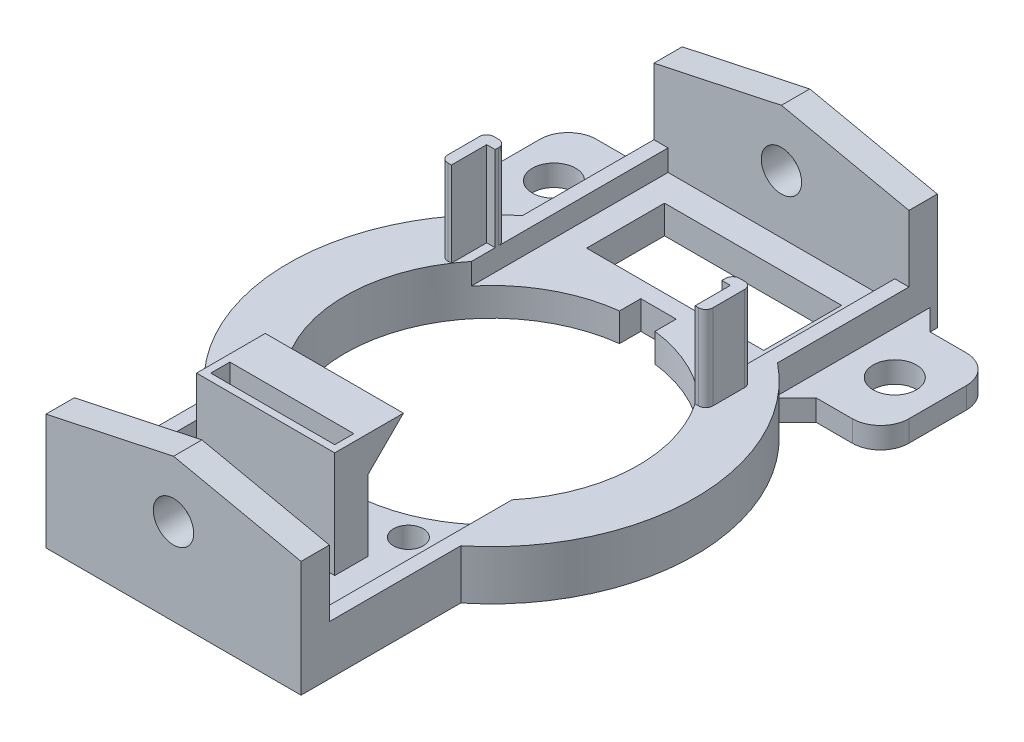
SolidWorks part; units mm, degrees
ref_plane "Front Plane" through (0, 0, 0) normal (0, 0, 1) x (1, 0, 0)
ref_plane "Top Plane" through (0, 0, 0) normal (0, 1, 0) x (1, 0, 0)
ref_plane "Right Plane" through (0, 0, 0) normal (1, 0, 0) x (0, 0, -1)
sketch "Sketch1" plane through (0, 0, 0) normal (0, 0, 1) x (1, 0, 0)
  line L3 (-18, 114.7896) -> (0, 114.7896)
  line L4 (0, 114.7896) -> (18, 114.7896)
  line L7 (0, 118.6383) -> (-38.0273, 110.5073) construction
  line L9 (38.0273, 110.5073) -> (0, 118.6383) construction
  line L11 (18, 114.7896) -> (18, 121.7896)
  line L12 (18, 121.7896) -> (16, 121.7896)
  line L13 (16, 121.7896) -> (16, 118.7896)
  line L14 (16, 118.7896) -> (-16, 118.7896)
  line L15 (-16, 118.7896) -> (-16, 121.7896)
  line L16 (-16, 121.7896) -> (-18, 121.7896)
  line L17 (-18, 121.7896) -> (-18, 114.7896)
  point P15 (0, 118.7896)
  dimension "D1" = 32
  dimension "D2" = 2
  dimension "D3" = 3
  dimension "D4" = 4
extrude "Boss-Extrude1" add sketch "Sketch1" along normal up to surface (89.8 mm away)
sketch "Sketch2" plane through (0, 114.7896, 0) normal (0, -1, 0) x (1, 0, 0)
  line L0 (18, 89.8) -> (18, 0) construction
  line L5 (-14, 54.9) -> (14, 54.9)
  line L6 (-14, 54.9) -> (-14, 34.9)
  line L7 (-14, 34.9) -> (14, 34.9)
  line L8 (14, 54.9) -> (14, 34.9)
  point P4 (0, 34.9)
  point P8 (18, 44.9)
  point P9 (14, 44.9)
  dimension "D1" = 4
  dimension "D2" = 20
extrude "Cut-Extrude1" [suppressed] cut sketch "Sketch2" against normal up to next
sketch "Sketch3" plane through (-18, 0, 0) normal (-1, 0, 0) x (0, 0, 1)
  line L0 (89.8, 121.7896) -> (0, 121.7896) construction
  line L1 (40.65, 118.7896) -> (49.15, 118.7896)
  line L2 (40.65, 118.7896) -> (40.65, 121.7896)
  line L3 (40.65, 121.7896) -> (49.15, 121.7896)
  line L4 (49.15, 118.7896) -> (49.15, 121.7896)
  line L5 (89.8, 118.7896) -> (0, 118.7896) construction
  point P9 (44.9, 121.7896)
  point P10 (44.9, 121.7896)
  dimension "D1" = 8.5
extrude "Cut-Extrude2" [suppressed] cut sketch "Sketch3" against normal through all
sketch "Sketch4" plane through (0, 118.7896, 0) normal (0, 1, 0) x (1, 0, 0)
  circle A0 centre (7.75, -23.25) radius 2.1 construction
  circle A4 centre (-7.75, -23.25) radius 2.1 construction
  circle A5 centre (7.75, -23.25) radius 2.1
  circle A6 centre (-7.75, -23.25) radius 2.1
extrude "Cut-Extrude3" [suppressed] cut sketch "Sketch4" against normal through all
ref_plane "Plane2" through (0, 0, 44.9) normal (0, 0, -1) x (-1, 0, 0)
sketch "Sketch5" plane through (0, 0, 0) normal (0, 0, 1) x (1, 0, 0)
  line L0 (-18, 114.7896) -> (-18, 131.1512)
  line L1 (-56.4, 122.9405) -> (0, 135) construction
  line L2 (-18, 131.1512) -> (0, 135)
  line L3 (0, 135) -> (18, 131.1512)
  line L4 (0, 135) -> (56.4, 122.9405) construction
  line L5 (18, 131.1512) -> (18, 114.7896)
  line L6 (18, 114.7896) -> (-18, 114.7896)
  line L7 (0.6273, 134.8659) -> (54.0273, 123.4479) construction
  line L8 (-54.0273, 123.4479) -> (-0.6273, 134.8659) construction
  circle A0 centre (0, 127) radius 2.85
  dimension "D1" = 5.7
  dimension "D2" = 8
extrude "Boss-Extrude2" add sketch "Sketch5" along normal blind 4
mirror "Mirror1" about plane through (0, 0, 44.9) normal (0, 0, -1) of "Boss-Extrude2"
sketch "Sketch6" plane through (0, 118.7896, 0) normal (0, 1, 0) x (1, 0, 0)
  line L1 (12.5, -19) -> (-12.5, -19)
  line L2 (12.5, -19) -> (12.5, -8)
  line L3 (12.5, -8) -> (-12.5, -8)
  line L4 (-12.5, -19) -> (-12.5, -8)
  point P4 (0, -8)
  dimension "D1" = 11
  dimension "D2" = 25
  dimension "D3" = 8
extrude "Cut-Extrude4" cut sketch "Sketch6" against normal through all
sketch "Sketch8" plane through (0, 118.7896, 0) normal (0, 1, 0) x (1, 0, 0)
  line L0 (16, -85.8) -> (-16, -85.8) construction
  line L1 (8.75, -75.8) -> (-8.75, -75.8)
  line L2 (8.75, -75.8) -> (8.75, -73.1)
  line L3 (8.75, -73.1) -> (-8.75, -73.1)
  line L4 (-8.75, -75.8) -> (-8.75, -73.1)
  line L5 (0, -89.8) -> (53.4, -89.8) construction
  line L6 (9.75, -72.1) -> (-9.75, -72.1)
  line L7 (-9.75, -76.8) -> (-9.75, -72.1)
  line L8 (9.75, -76.8) -> (-9.75, -76.8)
  line L9 (9.75, -76.8) -> (9.75, -72.1)
  point P6 (0, -85.8)
  point P7 (0, -75.8)
  dimension "D1" = 13
  dimension "D2" = 2.7
  dimension "D3" = 17.5
  dimension "D4" = 1
extrude "Boss-Extrude3" add sketch "Sketch8" along normal blind 15
sketch "Sketch9" plane through (-9.75, 0, 0) normal (-1, 0, 0) x (0, 0, 1)
  line L0 (72.1, 128.7896) -> (67.1, 133.7896)
  line L1 (72.1, 133.7896) -> (72.1, 118.7896) construction
  line L2 (67.1, 133.7896) -> (72.1, 133.7896)
  line L3 (72.1, 133.7896) -> (72.1, 128.7896)
  dimension "D1" = 5
  dimension "D2" = 45
extrude "Boss-Extrude4" add sketch "Sketch9" against normal up to surface (19.5 mm away) up to face at (9.75, 126.2896, 74.45)
sketch "Sketch13" plane through (0, 118.7896, 0) normal (0, 1, 0) x (1, 0, 0)
  line L4 (-8.75, -75.8) -> (8.75, -75.8)
  line L5 (8.75, -75.8) -> (8.75, -73.1)
  line L6 (8.75, -73.1) -> (-8.75, -73.1)
  line L7 (-8.75, -73.1) -> (-8.75, -75.8)
  line L8 (-8.75, -75.8) -> (8.75, -75.8)
  line L9 (8.75, -75.8) -> (8.75, -73.1)
  line L10 (8.75, -73.1) -> (-8.75, -73.1)
  line L11 (-8.75, -73.1) -> (-8.75, -75.8)
  dimension "D1" = 0
extrude "Cut-Extrude5" cut sketch "Sketch13" against normal through all
sketch "Sketch10" [suppressed] plane through (0, 121.7896, 0) normal (0, 1, 0) x (1, 0, 0)
  line L1 (16, -59.15) -> (18, -59.15)
  line L2 (16, -59.15) -> (16, -49.15)
  line L3 (16, -49.15) -> (18, -49.15)
  line L4 (18, -59.15) -> (18, -49.15)
  line L5 (0, -1000) -> (0, 49000) construction
  line L6 (-16, -49.15) -> (-18, -49.15)
  line L7 (-16, -59.15) -> (-16, -49.15)
  line L8 (-16, -59.15) -> (-18, -59.15)
  line L9 (-18, -59.15) -> (-18, -49.15)
  dimension "D1" = 10
extrude "Boss-Extrude5" [suppressed] add sketch "Sketch10" along normal up to surface (12 mm away)
sketch "Sketch14" plane through (0, 114.7896, 0) normal (0, 1, 0) x (1, 0, 0)
  line L0 (-18, -85.8) -> (-18, -4) construction
  line L1 (-18, -4) -> (-30.1, -4)
  line L2 (-18, -4) -> (-18, -20.1)
  line L3 (-18, -20.1) -> (-30.1, -20.1)
  line L4 (-30.1, -4) -> (-30.1, -20.1)
  circle A0 centre (-24.05, -12.05) radius 3.05
  point P9 (-30.1, -12.05)
  point P10 (-24.05, -20.1)
  dimension "D1" = 6.1
  dimension "D2" = 3
  dimension "D3" = 5
extrude "Boss-Extrude7" add sketch "Sketch14" along normal blind 3
mirror "Mirror2" about plane through (0, 0, 0) normal (1, 0, 0) of "Boss-Extrude7"
chamfer "Chamfer1" distance 3 angle 45 4 edges at (-18, 116.2896, 20.1) (-18, 116.2896, 4) (18, 116.2896, 4) (18, 116.2896, 20.1)
sketch "Sketch17" plane through (0, 118.7896, 0) normal (0, 1, 0) x (1, 0, 0)
  circle A0 centre (0, -81.15) radius 2.1
  circle A1 centre (0, -81.15) radius 2.85 construction
  dimension "D1" = 4.2
extrude "Cut-Extrude6" cut sketch "Sketch17" against normal through all
sketch "Sketch19" plane through (0, 114.7896, 0) normal (0, -1, 0) x (1, 0, 0)
  line L0 (18, 67.2537) -> (18, 55.122)
  line L2 (-16, 68.7262) -> (-16, 58.0335)
  line L3 (-18, 34.678) -> (-18, 22.5463)
  line L4 (18, 22.5463) -> (18, 34.678)
  line L6 (-18, 85.8) -> (-18, 4) construction
  line L7 (18, 85.8) -> (18, 4) construction
  line L8 (-16, 85.8) -> (-16, 4) construction
  arc A0 (-16, 58.0335) -> (-18, 34.678) centre (0, 44.9) ccw
  arc A1 (-16, 68.7262) -> (-18, 22.5463) centre (0, 44.9) ccw
  circle A2 centre (0, 44.9) radius 20.2 construction
  arc A3 (18, 22.5463) -> (18, 67.2537) centre (0, 44.9) ccw
  arc A4 (18, 34.678) -> (18, 55.122) centre (0, 44.9) ccw
  dimension "D1" = 0.5
  dimension "D2" = 8
extrude "Boss-Extrude8" add sketch "Sketch19" against normal up to surface (7 mm away) up to face at (-17, 121.7896, 44.9)
sketch "Sketch20" plane through (0, 114.7896, 0) normal (0, -1, 0) x (1, 0, 0)
  circle A0 centre (0, 44.9) radius 20.7
  arc A1 (18, 34.678) -> (18, 55.122) centre (0, 44.9) ccw construction
extrude "Cut-Extrude7" cut sketch "Sketch20" against normal up to next
fillet "Fillet1" radius 4 4 edges at (-30.1, 116.2896, 4) (-30.1, 116.2896, 20.1) (30.1, 116.2896, 4) (30.1, 116.2896, 20.1)
sketch "Sketch21" plane through (0, 118.7896, 0) normal (0, 1, 0) x (1, 0, 0)
  circle A0 centre (-10.2696, -66.9233) radius 2.1 construction
  circle A1 centre (10.2696, -66.9233) radius 2.1 construction
  circle A2 centre (-10.2696, -66.9233) radius 2.1
  circle A3 centre (10.2696, -66.9233) radius 2.1
extrude "Cut-Extrude8" cut sketch "Sketch21" against normal through all
sketch "Sketch22" plane through (0, 118.7896, 0) normal (0, 1, 0) x (1, 0, 0)
  line L0 (-1000, -44.9) -> (49000, -44.9) construction
  line L1 (-2.5, -65.4485) -> (2.5, -65.4485)
  line L2 (-2.5, -65.4485) -> (-2.5, -68.4485)
  line L3 (-2.5, -68.4485) -> (2.5, -68.4485)
  line L4 (2.5, -65.4485) -> (2.5, -68.4485)
  line L5 (2.5, -24.3515) -> (2.5, -21.3515)
  line L6 (-2.5, -21.3515) -> (2.5, -21.3515)
  line L7 (-2.5, -24.3515) -> (-2.5, -21.3515)
  line L8 (-2.5, -24.3515) -> (2.5, -24.3515)
  arc A0 (-16, -58.0335) -> (16, -58.0335) centre (0, -44.9) ccw construction
  dimension "D1" = 5
  dimension "D2" = 3
extrude "Cut-Extrude9" cut sketch "Sketch22" against normal through all
sketch "Sketch23" plane through (0, 121.7896, 0) normal (0, 1, 0) x (1, 0, 0)
  line L0 (-17, -33.3) -> (-17, -28.6) construction
  line L1 (-18.7, -26.9) -> (-16, -26.9)
  line L2 (-18.7, -26.9) -> (-18.7, -33.3826)
  line L3 (-18.7, -33.3826) -> (-17.2, -33.3826)
  line L4 (-17.2, -28.4) -> (-17.2, -33.3826)
  line L5 (-12.4996, -26.9) -> (-16, -26.9) construction
  line L6 (-12.4996, -26.9) -> (-12.4996, -28.4) construction
  line L7 (-12.4996, -28.4) -> (-16, -28.4) construction
  line L9 (-17, -28.6) -> (-14.5, -28.6) construction
  line L10 (-16, -31.7665) -> (-16, -4) construction
  line L11 (-16, -26.9) -> (-16, -28.4)
  line L12 (-16, -28.4) -> (-17.2, -28.4)
  arc A0 (-16, -31.7665) -> (-16, -58.0335) centre (0, -44.9) ccw construction
  arc A1 (-2.5, -24.3515) -> (-16, -31.7665) centre (0, -44.9) ccw construction
  dimension "D1" = 0.2
  dimension "D2" = 0.2
  dimension "D3" = 1.5
  dimension "D4" = 1.5
extrude "Boss-Extrude9" add sketch "Sketch23" along normal up to surface (12 mm away)
fillet "Fillet2" radius 1 3 edges at (-18.7, 127.7896, 33.3826) (-16, 127.7896, 26.9) (-18.7, 127.7896, 26.9)
mirror "Mirror3" about plane through (0, 0, 0) normal (1, 0, 0) of "Fillet2", "Boss-Extrude9"
equation "\"width\"= 24"
equation "\"thk\"= 3"
equation "\"holesize\"= 4.2"
equation "\"holedistance\"= ( 20 + 12 ) / 2"
equation "\"threaded_hole\"= 3.9"
equation "\"fillet_radius\"= 2"
equation "\"ground_clearance\"= 25"
equation "\"tire_thk\"= 3"
equation "\"innerwheel_diam\" = \"wheel_diam\"-2*\"tire_thk\""
equation "\"innerwheel_thk\"= 8"
equation "\"wheel_diam\"= 2*(\"width\"/2+\"ground_clearance\")"
equation "\"coloursensor_holesize\"= 2.65"
equation "\"hole_to_edge\" = 4"
equation "\"D1@Sketch5\"=\"M4_insert_diam\""
equation "\"D1@Sketch17\"=\"holesize\""
equation "\"M4_insert_diam\"= 5.7"
